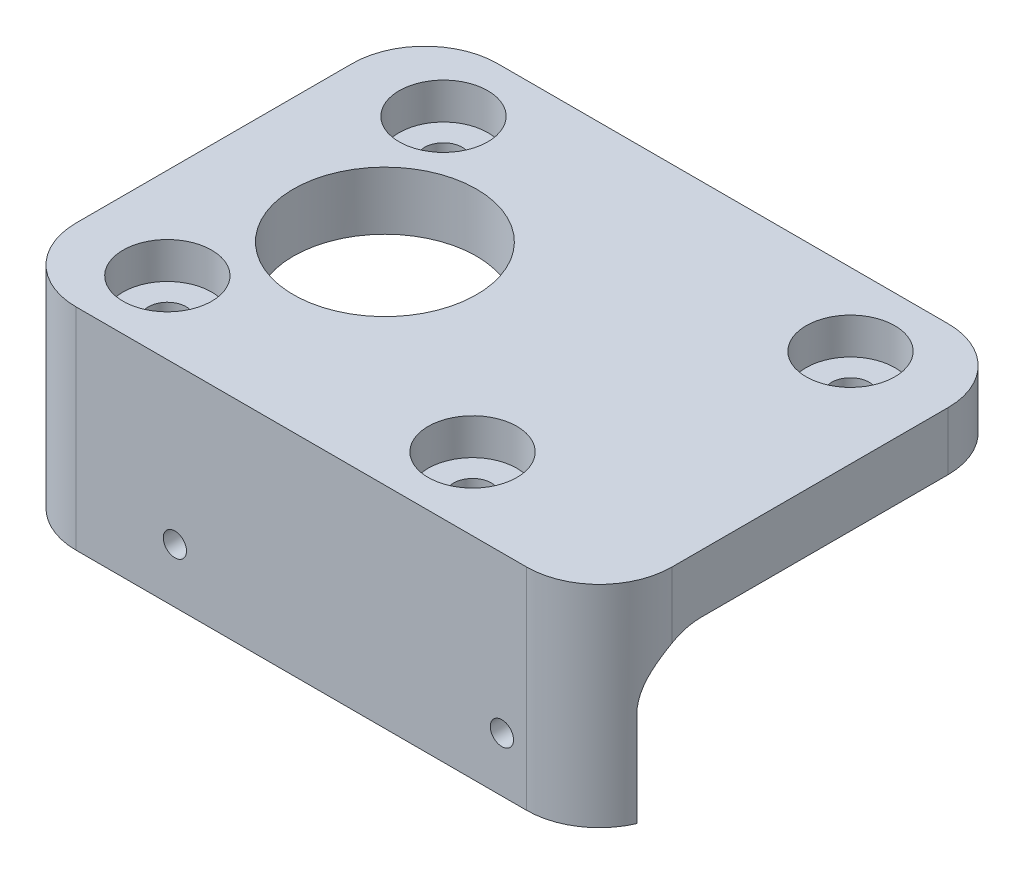
SolidWorks part; units mm, degrees
ref_plane "Front Plane" through (0, 0, 0) normal (0, 0, 1) x (1, 0, 0)
ref_plane "Top Plane" through (0, 0, 0) normal (0, 1, 0) x (1, 0, 0)
ref_plane "Right Plane" through (0, 0, 0) normal (1, 0, 0) x (0, 0, -1)
sketch "Sketch1" plane through (0, 0, 0) normal (0, 1, 0) x (1, 0, 0)
  line L1 (0, 0) -> (82, 0)
  line L2 (0, 0) -> (0, 58)
  line L3 (0, 58) -> (82, 58)
  line L4 (82, 0) -> (82, 58)
  line L5 (0, 58) -> (82, 58) construction
  line L6 (0, 58) -> (0, 118.9)
  line L7 (0, 29) -> (82, 29) construction
  line L8 (0, 118.9) -> (82, 118.9)
  line L9 (0, 48) -> (82, 48) construction
  line L10 (82, 58) -> (82, 118.9)
  line L11 (0, 10) -> (82, 10) construction
  circle A4 centre (12.5611, 48) radius 6.1
  circle A5 centre (12.5611, 10) radius 6.1
  circle A6 centre (54.5611, 10) radius 6.1
  circle A7 centre (68.57, 48) radius 6.1
  circle A8 centre (23.5, 29) radius 12.6
  dimension "D10" = 12.2
  dimension "D12" = 42
  dimension "D13" = 40.5
  dimension "D14" = 25.2
  dimension "D15" = 23.5
  dimension "D16" = 45.07
  dimension "D1" = 58
  dimension "D2" = 82
  dimension "D3" = 60.9
  dimension "D8" = 38
  dimension "D9" = 19
extrude "Boss-Extrude1" add sketch "Sketch1" along normal blind 5 contours L1 L4 L3 L2 A8 A7 A6 A5 A4 region at (43.7889, 0, -29)
sketch "Sketch2" plane through (0, 5, 0) normal (0, 1, 0) x (1, 0, 0)
  line L8 (0, 0) -> (82, 0)
  line L9 (0, 0) -> (0, 58)
  line L10 (0, 58) -> (82, 58)
  line L11 (82, 0) -> (82, 58)
  circle A0 centre (12.5611, 48) radius 2.6
  circle A1 centre (68.57, 48) radius 2.6
  circle A2 centre (54.5611, 10) radius 2.6
  circle A3 centre (12.5611, 10) radius 2.6
  circle A4 centre (23.5, 29) radius 12.6
  circle A5 centre (23.5, 29) radius 12.6 construction
  dimension "D1" = 5.2
extrude "Boss-Extrude3" add sketch "Sketch2" along normal blind 3
sketch "Sketch3" plane through (0, 8, 0) normal (0, 1, 0) x (1, 0, 0)
  line L0 (82, 58) -> (0, 58) construction
  line L1 (0, 58) -> (82, 58)
  line L2 (0, 58) -> (0, 52)
  line L3 (0, 52) -> (82, 52)
  line L4 (82, 58) -> (82, 52)
  line L5 (0, 58) -> (0, 0) construction
  line L7 (82, 0) -> (82, 58) construction
  dimension "D1" = 6
extrude "Boss-Extrude4" add sketch "Sketch3" along normal blind 21
fillet "Fillet7" radius 5 1 edges at (41, 8, -52)
sketch "Sketch6" plane through (0, 8, 0) normal (0, 1, 0) x (1, 0, 0)
  circle A0 centre (12.5611, 48) radius 4.5
  circle A1 centre (68.57, 48) radius 4.5
  dimension "D1" = 9
extrude "Cut-Extrude1" cut sketch "Sketch6" along normal through all
sketch "Sketch8" plane through (0, 8, 0) normal (0, 1, 0) x (1, 0, 0)
  line L0 (0, 23.5) -> (82, 23.5)
  line L1 (0, 47) -> (0, 0) construction
  line L2 (82, 0) -> (82, 47) construction
ref_plane "Plane1" through (0, 0, -28.5) normal (0, 0, 1) x (1, 0, 0)
sketch "Sketch9" plane through (0, 8, 0) normal (0, 1, 0) x (1, 0, 0)
  line L0 (82, 0) -> (82, 47) construction
  line L1 (0, 0) -> (82, 0)
  line L2 (0, 0) -> (0, 6)
  line L3 (0, 6) -> (82, 6)
  line L4 (82, 0) -> (82, 6)
  dimension "D1" = 6
extrude "Boss-Extrude6" add sketch "Sketch9" along normal up to surface (21 mm away) up to face at (40.7828, 29, -53.625)
fillet "Fillet8" radius 10 4 edges at (82, 14.5, -58) (82, 14.5, 0) (0, 14.5, 0) (0, 14.5, -58)
fillet "Fillet9" radius 8 1 edges at (41, 8, -6)
sketch "Sketch11" plane through (0, 8, 0) normal (0, 1, 0) x (1, 0, 0)
  circle A0 centre (12.5611, 10) radius 4.5
  circle A1 centre (54.5611, 10) radius 4.5
  dimension "D1" = 9
extrude "Cut-Extrude3" cut sketch "Sketch11" along normal through all
sketch "Sketch12" plane through (0, 8, 0) normal (0, 1, 0) x (1, 0, 0)
  line L0 (0, 47) -> (0, 14) construction
  line L1 (0, 47) -> (82, 47)
  line L2 (0, 47) -> (0, 58)
  line L3 (0, 58) -> (82, 58)
  line L4 (82, 47) -> (82, 58)
  line L5 (82, 14) -> (82, 47) construction
  line L6 (72, 58) -> (10, 58) construction
  line L7 (8.1736, 47) -> (0, 47) construction
extrude "Cut-Extrude4" cut sketch "Sketch12" along normal through all
mirror "Mirror1" about plane through (0, 0, 0) normal (0, 1, 0) of bodies 117
sketch "Sketch13" plane through (0, 29, 0) normal (0, 1, 0) x (1, 0, 0)
  line L1 (0, 0) -> (82, 0)
  line L2 (0, 0) -> (0, 58)
  line L3 (0, 58) -> (82, 58)
  line L4 (82, 0) -> (82, 58)
  line L5 (82, 14) -> (82, 48) construction
  line L6 (72, 58) -> (10, 58) construction
extrude "Cut-Extrude5" cut sketch "Sketch13" against normal blind 29
sketch "Sketch14" plane through (0, 0, 0) normal (0, 0, 1) x (1, 0, 0)
  circle A0 centre (23.6, -21.5) radius 1.6
  circle A1 centre (68.6, -21.5) radius 1.6
  circle A2 centre (23.6, -21.5) radius 1.6 construction
  circle A3 centre (68.6, -21.5) radius 1.6 construction
extrude "Cut-Extrude6" cut sketch "Sketch14" against normal through all
